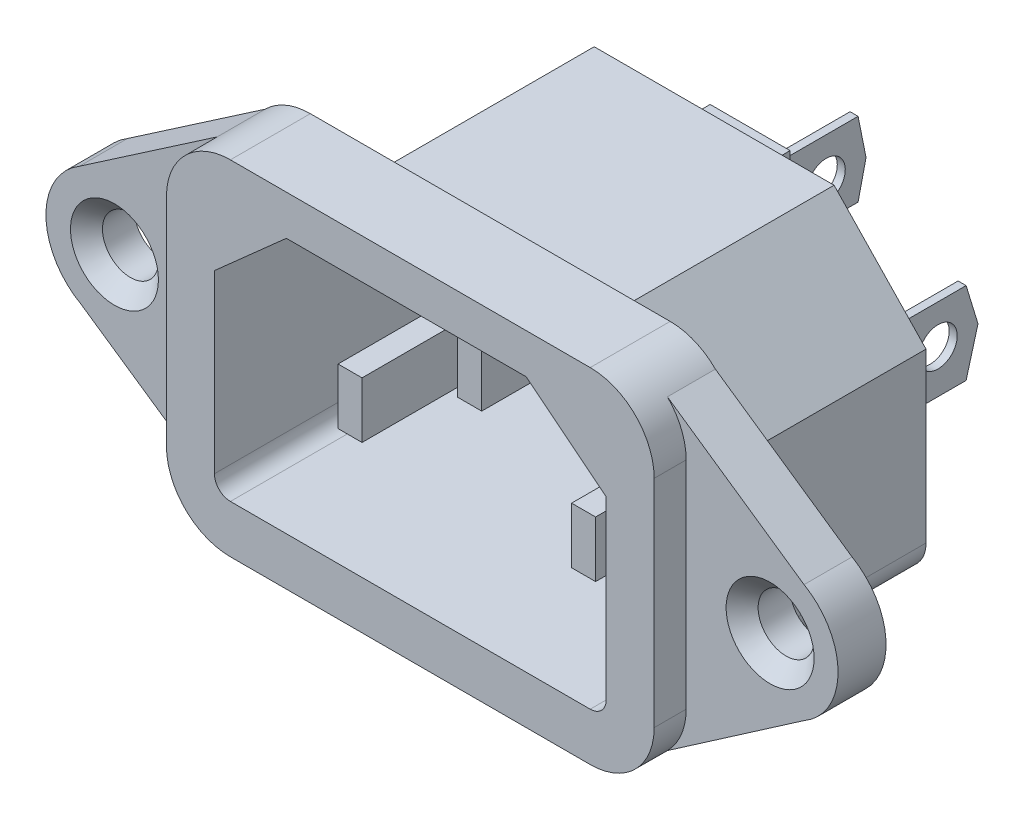
SolidWorks part; units mm, degrees
ref_plane "Спереди" through (0, 0, 0) normal (0, 0, 1) x (1, 0, 0)
ref_plane "Сверху" through (0, 0, 0) normal (0, 1, 0) x (1, 0, 0)
ref_plane "Справа" through (0, 0, 0) normal (1, 0, 0) x (0, 0, -1)
sketch "Эскиз1" plane through (0, 0, 0) normal (0, 0, 1) x (1, 0, 0)
  line L0 (23.0556, -0.5833) -> (-26.4444, -0.5833) construction
  line L1 (-12.9444, 10.1667) -> (9.5556, 10.1667)
  line L2 (-16.9444, 6.1667) -> (-16.9444, -7.3333)
  line L3 (-12.9444, -11.3333) -> (9.5556, -11.3333)
  line L4 (13.5556, 6.1667) -> (13.5556, -7.3333)
  line L5 (-15.7729, 8.9951) -> (-24.3879, 3.0982)
  line L6 (-24.2767, -4.329) -> (-15.7729, -10.1618)
  line L7 (12.384, 8.9951) -> (20.9289, 3.0982)
  line L8 (20.9289, -4.2649) -> (12.384, -10.1618)
  arc A0 (-12.9444, 10.1667) -> (-16.9444, 6.1667) centre (-12.9444, 6.1667) ccw
  arc A1 (-16.9444, -7.3333) -> (-12.9444, -11.3333) centre (-12.9444, -7.3333) ccw
  arc A2 (9.5556, -11.3333) -> (13.5556, -7.3333) centre (9.5556, -7.3333) ccw
  arc A3 (9.5556, 10.1667) -> (13.5556, 6.1667) centre (9.5556, 6.1667) cw
  circle A5 centre (-22.1944, -0.5833) radius 1.75
  circle A6 centre (18.8056, -0.5833) radius 1.75
  arc A7 (20.9289, -4.2649) -> (20.9289, 3.0982) centre (18.8056, -0.5833) ccw
  arc A8 (-24.3879, 3.0982) -> (-24.2767, -4.329) centre (-22.1944, -0.5833) ccw
  point P6 (-16.9444, 10.1667)
  point P11 (13.5556, -11.3333)
  point P14 (13.5556, 10.1667)
  point P21 (-16.9444, -0.5833)
  dimension "D3" = 4
  dimension "D5" = 4.25
  dimension "D6" = 4.25
  dimension "D1" = 30.5
  dimension "D2" = 21.5
  dimension "D4" = 9.5
  dimension "D7" = 5.25
  dimension "D8" = 5.25
extrude "Бобышка-Вытянуть1" add sketch "Эскиз1" against normal blind 3 contours L4 L0 L2 A1 L3 A2 | L0 L4 A3 L1 A0 L2 | A7 L0 A6 L4 A2 L8 | L0 A7 L7 A3 L4 A6 | L5 A8 L6 A1 L2 A5 A0 region at (17.0838, -3.9737, 0) region at (17.0838, 2.8071, 0) region at (-1.6944, -5.8625, 0) region at (-1.6944, 4.6958, 0) region at (-17.1639, -3.9583, 0)
sketch "Эскиз3" plane through (0, 0, 0) normal (0, 0, 1) x (1, 0, 0)
  line L0 (-12.9444, 10.1667) -> (9.5556, 10.1667) construction
  line L1 (-12.9444, 10.1667) -> (9.5556, 10.1667)
  line L2 (-16.9444, 6.1667) -> (-16.9444, -7.3333)
  line L3 (-12.9444, -11.3333) -> (9.5556, -11.3333)
  line L4 (13.5556, 6.1667) -> (13.5556, -7.3333)
  arc A0 (9.5556, 10.1667) -> (13.5556, 6.1667) centre (9.5556, 6.1667) cw
  arc A1 (9.5556, -11.3333) -> (13.5556, -7.3333) centre (9.5556, -7.3333) ccw
  arc A2 (-16.9444, -7.3333) -> (-12.9444, -11.3333) centre (-12.9444, -7.3333) ccw
  arc A3 (-12.9444, 10.1667) -> (-16.9444, 6.1667) centre (-12.9444, 6.1667) ccw
  point P4 (-1.6944, 10.1667)
  point P7 (-1.6944, 10.1667)
  point P10 (13.5556, 10.1667)
  point P15 (-16.9444, -11.3333)
  point P18 (-16.9444, 10.1667)
  dimension "D3" = 4
  dimension "D1" = 30.5
  dimension "D2" = 21.5
extrude "Бобышка-Вытянуть2" add sketch "Эскиз3" along normal blind 2
sketch "Эскиз4" plane through (0, 0, -3) normal (0, 0, -1) x (-1, 0, 0)
  line L0 (1.7119, 8.6668) -> (1.7119, -9.8333) construction
  line L1 (-5.8056, 8.6667) -> (9.1944, 8.6667)
  line L2 (-11.5556, 2.6667) -> (-11.5556, -7.8333)
  line L3 (-9.5556, -9.8333) -> (12.9795, -9.8333)
  line L4 (14.9795, 2.6667) -> (14.9795, -7.8333)
  line L5 (12.9444, 10.1667) -> (-9.5556, 10.1667) construction
  line L6 (12.9444, -11.3333) -> (-9.5556, -11.3333) construction
  line L7 (-11.2855, 2.6667) -> (-11.5556, 2.6667) construction
  line L11 (-11.5556, 2.6667) -> (-5.8056, 8.6667)
  line L12 (9.1944, 8.6667) -> (14.9795, 2.6667)
  arc A0 (-20.9289, 3.0982) -> (-20.9289, -4.2649) centre (-18.8056, -0.5833) ccw construction
  arc A1 (24.2767, -4.329) -> (24.3879, 3.0982) centre (22.1944, -0.5833) ccw construction
  arc A2 (-11.5556, -7.8333) -> (-9.5556, -9.8333) centre (-9.5556, -7.8333) ccw
  arc A3 (12.9795, -9.8333) -> (14.9795, -7.8333) centre (12.9795, -7.8333) ccw
  point P9 (-23.0556, -0.5833)
  point P12 (1.6944, 10.1667)
  point P17 (26.4795, -0.6475)
  point P19 (1.7119, 6.1202)
  dimension "D5" = 2
  dimension "D1" = 11.5
  dimension "D2" = 11.5
  dimension "D3" = 1.5
  dimension "D4" = 1.5
extrude "Бобышка-Вытянуть3" add sketch "Эскиз4" along normal blind 14
sketch "Эскиз5" plane through (0, 0, -3) normal (0, 0, -1) x (-1, 0, 0)
  line L0 (-17.1431, 3.368) -> (-10.047, 8.2024)
  line L1 (-10.047, 8.2024) -> (-8.1409, 8.2024)
  line L2 (-8.1409, 8.2024) -> (-13.1129, 2.8675)
  line L3 (-13.1129, 2.8675) -> (-13.1129, -7.3555)
  line L4 (-13.1129, -7.3555) -> (-17.1431, -4.5346)
  line L5 (20.5354, 3.368) -> (13.5142, 8.2024)
  line L6 (13.5142, 8.2024) -> (11.5035, 8.2024)
  line L7 (11.5035, 8.2024) -> (16.8383, 2.8675)
  line L8 (16.8383, 2.8675) -> (16.8383, -7.0285)
  line L9 (16.8383, -7.0285) -> (20.5354, -4.5346)
  arc A0 (-17.1431, -4.5346) -> (-17.1431, 3.368) centre (-18.8056, -0.5833) ccw
  arc A1 (20.5354, 3.368) -> (20.5354, -4.5346) centre (22.1944, -0.5833) ccw
extrude "Вырез-Вытянуть1" cut sketch "Эскиз5" against normal blind 1
chamfer "Фаска1" distance 1 angle 45 1 edges at (20.5556, -0.5833, 0)
chamfer "Фаска2" distance 1 angle 45 1 edges at (-20.4444, -0.5833, 0)
sketch "Эскиз6" plane through (0, 0, -17) normal (0, 0, -1) x (-1, 0, 0)
  line L0 (9.1944, 8.6667) -> (-5.8056, 8.6667) construction
  line L1 (-8.0556, 1.6667) -> (-3.0556, 1.6667)
  line L2 (-8.0556, 1.6667) -> (-8.0556, -8.3333)
  line L3 (-8.0556, -8.3333) -> (-3.0556, -8.3333)
  line L4 (-3.0556, 1.6667) -> (-3.0556, -8.3333)
  line L5 (-8.0556, 1.6667) -> (-3.0556, -8.3333) construction
  line L6 (-8.0556, -8.3333) -> (-3.0556, 1.6667) construction
  line L7 (-1.0556, 7.1667) -> (3.9444, 7.1667)
  line L8 (-1.0556, 7.1667) -> (-1.0556, -2.8333)
  line L9 (-1.0556, -2.8333) -> (3.9444, -2.8333)
  line L10 (3.9444, 7.1667) -> (3.9444, -2.8333)
  line L11 (-1.0556, 7.1667) -> (3.9444, -2.8333) construction
  line L12 (-1.0556, -2.8333) -> (3.9444, 7.1667) construction
  line L13 (6.4795, 1.6667) -> (11.4795, 1.6667)
  line L14 (6.4795, 1.6667) -> (6.4795, -8.3333)
  line L15 (6.4795, -8.3333) -> (11.4795, -8.3333)
  line L16 (11.4795, 1.6667) -> (11.4795, -8.3333)
  line L17 (6.4795, 1.6667) -> (11.4795, -8.3333) construction
  line L18 (6.4795, -8.3333) -> (11.4795, 1.6667) construction
  line L19 (9.1944, 8.6667) -> (-5.8056, 8.6667) construction
  line L20 (-11.5556, 2.6667) -> (-11.5556, -7.8333) construction
  line L21 (14.9795, -7.8333) -> (14.9795, 2.6667) construction
  line L22 (-9.5556, -9.8333) -> (12.9795, -9.8333) construction
  line L23 (-11.5556, 2.6667) -> (-11.5556, -7.8333) construction
  point P0 (-5.5556, -3.3333)
  point P5 (1.4444, 2.1667)
  point P10 (8.9795, -3.3333)
  dimension "D1" = 5
  dimension "D2" = 10
  dimension "D3" = 5
  dimension "D4" = 10
  dimension "D5" = 5
  dimension "D6" = 10
  dimension "D7" = 7
  dimension "D8" = 7
  dimension "D9" = 3.5
  dimension "D10" = 3.5
  dimension "D11" = 7
  dimension "D12" = 10.5
extrude "Бобышка-Вытянуть4" add sketch "Эскиз6" along normal blind 2
sketch "Эскиз7" plane through (0, 0, -19) normal (0, 0, -1) x (-1, 0, 0)
  line L0 (-8.0556, -8.3333) -> (-3.0556, -8.3333) construction
  line L1 (-5.8056, 0.6667) -> (-5.3056, 0.6667)
  line L2 (-5.8056, 0.6667) -> (-5.8056, -7.3333)
  line L3 (-5.8056, -7.3333) -> (-5.3056, -7.3333)
  line L4 (-5.3056, 0.6667) -> (-5.3056, -7.3333)
  line L5 (-8.0556, 1.6667) -> (-8.0556, -8.3333) construction
  line L7 (11.4795, -8.3333) -> (11.4795, 1.6667) construction
  line L8 (1.1944, 6.1667) -> (1.6944, 6.1667)
  line L9 (1.1944, 6.1667) -> (1.1944, -1.8333)
  line L10 (1.1944, -1.8333) -> (1.6944, -1.8333)
  line L11 (1.6944, 6.1667) -> (1.6944, -1.8333)
  line L12 (8.7295, 0.6667) -> (9.2295, 0.6667)
  line L13 (8.7295, 0.6667) -> (8.7295, -7.3333)
  line L14 (8.7295, -7.3333) -> (9.2295, -7.3333)
  line L15 (9.2295, 0.6667) -> (9.2295, -7.3333)
  line L16 (3.9444, -2.8333) -> (3.9444, 7.1667) construction
  line L17 (-1.0556, -2.8333) -> (3.9444, -2.8333) construction
  line L18 (6.4795, -8.3333) -> (11.4795, -8.3333) construction
  dimension "D1" = 0.5
  dimension "D2" = 8
  dimension "D3" = 1
  dimension "D4" = 2.25
  dimension "D5" = 0.5
  dimension "D6" = 8
  dimension "D7" = 0.5
  dimension "D8" = 8
  dimension "D9" = 2.25
  dimension "D10" = 2.25
  dimension "D11" = 1
  dimension "D12" = 1
extrude "Бобышка-Вытянуть5" add sketch "Эскиз7" along normal mid plane 14
sketch "Эскиз8" plane through (-9.2295, 0, 0) normal (-1, 0, 0) x (0, 0, 1)
  line L0 (-26, -3.3333) -> (-19, -3.3333) construction
  line L1 (-26, -3.3333) -> (-25.8529, -5.083)
  line L2 (-25.8529, -5.083) -> (-20.6676, -5.083)
  line L3 (-20.6676, -5.083) -> (-20.2818, -5.4689)
  line L4 (-19, -7.048) -> (-19, -7.3333)
  line L5 (-19, -7.3333) -> (-19, 0.6667) construction
  line L6 (-26, -7.3333) -> (-19, -7.3333) construction
  line L7 (-19, -7.3333) -> (-26, -7.3333)
  line L12 (-20.2818, -5.4689) -> (-19.1592, -5.4689)
  line L13 (-19.1592, -5.4689) -> (-20.0283, -7.1824)
  line L14 (-20.0283, -7.1824) -> (-19, -7.048)
  line L15 (-26, -7.3333) -> (-26, 0.6667)
  line L16 (-19, 0.6667) -> (-26, 0.6667)
  line L17 (-19, 0.3813) -> (-19, 0.6667)
  line L18 (-20.0283, 0.5157) -> (-19, 0.3813)
  line L19 (-19.1592, -1.1978) -> (-20.0283, 0.5157)
  line L20 (-20.2818, -1.1978) -> (-19.1592, -1.1978)
  line L21 (-20.6676, -1.5836) -> (-20.2818, -1.1978)
  line L22 (-25.8529, -1.5836) -> (-20.6676, -1.5836)
  line L23 (-26, -3.3333) -> (-25.8529, -1.5836)
  circle A0 centre (-23.4767, -3.3333) radius 1.2
  line M15 (-19, -7.3333) -> (-19, 0.6667)
  line M16 (-19, 0.6667) -> (-26, 0.6667)
  line M17 (-26, 0.6667) -> (-26, -7.3333)
  line M18 (-26, -7.3333) -> (-19, -7.3333)
extrude "Вырез-Вытянуть2" cut sketch "Эскиз8" against normal blind 3 contours L23 L22 L21 L20 L19 L18 M17 M15 M16 | L14 L13 L12 L3 L2 L1 M17 M18 M15 | A0 region at (-9.2295, -6.2115, -22.8481) region at (-9.2295, -0.4552, -22.8481)
sketch "Эскиз11" plane through (-1.6944, 0, 0) normal (-1, 0, 0) x (0, 0, 1)
  line L0 (-26, 2.1667) -> (-19, 2.1667) construction
  line L1 (-26, -1.8333) -> (-26, 6.1667) construction
  line L2 (-19, -1.8333) -> (-19, 6.1667) construction
  line L3 (-25.5002, 0) -> (-26, 2.1667)
  line L4 (-26, 6.1667) -> (-19, 6.1667)
  line L5 (-26, 6.1667) -> (-26, 4.6488)
  line L6 (-25.5002, 4.6488) -> (-19, 4.6488)
  line L7 (-19, 6.1667) -> (-19, 4.6488)
  line L8 (-26, -1.8333) -> (-19, -1.8333)
  line L9 (-26, -1.8333) -> (-26, 0)
  line L10 (-25.5002, 0) -> (-19, 0)
  line L11 (-19, -1.8333) -> (-19, 0)
  line L12 (-26, 2.1667) -> (-26, 0)
  line L13 (-26, 2.1667) -> (-25.5002, 4.6488)
  line L14 (-26, 2.1667) -> (-26, 4.6488)
  circle A0 centre (-23.5, 2.1667) radius 1.2
  line M14 (-19, -1.8333) -> (-19, 6.1667)
  line M15 (-19, 6.1667) -> (-26, 6.1667)
  line M16 (-26, 6.1667) -> (-26, -1.8333)
  line M17 (-26, -1.8333) -> (-19, -1.8333)
  dimension "D1" = 2.5
extrude "Вырез-Вытянуть3" cut sketch "Эскиз11" against normal blind 3 contours L0 A0 | A0 L0 | L13 L6 M16 M14 M15 | L10 L3 M16 M17 M14 region at (-1.6944, 1.6574, -23.5) region at (-1.6944, 2.676, -23.5) region at (-1.6944, -0.8503, -22.6349) region at (-1.6944, 5.3202, -22.6839)
sketch "Эскиз12" plane through (5.3056, 0, 0) normal (-1, 0, 0) x (0, 0, 1)
  line L0 (-26, -3.3333) -> (-19, -3.3333) construction
  line L1 (-26, -7.3333) -> (-26, 0.6667) construction
  line L2 (-19, -7.3333) -> (-19, 0.6667) construction
  line L3 (-25.2563, -6.0356) -> (-26, -3.3333)
  line L4 (-26, -7.3333) -> (-19, -7.3333)
  line L5 (-26, -7.3333) -> (-26, -6.0356)
  line L6 (-25.2563, -6.0356) -> (-19, -6.0356)
  line L7 (-19, -7.3333) -> (-19, -6.0356)
  line L8 (-26, 0.6667) -> (-19, 0.6667)
  line L9 (-26, 0.6667) -> (-26, -0.8964)
  line L10 (-25.2563, -0.8964) -> (-19, -0.8964)
  line L11 (-19, 0.6667) -> (-19, -0.8964)
  line L12 (-26, -3.3333) -> (-26, -6.0356)
  line L13 (-26, -3.3333) -> (-25.2563, -0.8964)
  line L14 (-26, -3.3333) -> (-26, -0.8964)
  circle A0 centre (-23.5, -3.3333) radius 1.2
  line M13 (-19, -7.3333) -> (-19, 0.6667)
  line M14 (-19, 0.6667) -> (-26, 0.6667)
  line M15 (-26, 0.6667) -> (-26, -7.3333)
  line M16 (-26, -7.3333) -> (-19, -7.3333)
  dimension "D1" = 2.5
extrude "Вырез-Вытянуть4" cut sketch "Эскиз12" against normal blind 3 contours L13 L10 M15 M13 M14 | L6 L3 M15 M16 M13 | L0 A0 | A0 L0 region at (5.3056, -3.8426, -23.5) region at (5.3056, -2.824, -23.5) region at (5.3056, -6.5301, -22.8239) region at (5.3056, -0.2368, -22.7487)
sketch "Эскиз15" plane through (0, 0, 2) normal (0, 0, 1) x (1, 0, 0)
  line L0 (9.5556, 10.1667) -> (-12.9444, 10.1667) construction
  line L1 (-9.4444, 7.6667) -> (5.5556, 7.6667)
  line L2 (-13.9444, 3.6667) -> (-13.9444, -7.3333)
  line L3 (-12.9444, -8.3333) -> (9.5556, -8.3333)
  line L4 (10.5556, 3.6667) -> (10.5556, -7.3333)
  line L5 (-16.9444, 6.1667) -> (-16.9444, -7.3333) construction
  line L10 (-1.6944, -8.3333) -> (-1.6944, 7.6667) construction
  line L14 (-9.4444, 7.6667) -> (-13.9444, 3.6667)
  line L15 (5.5556, 7.6667) -> (10.5556, 3.6667)
  arc A0 (9.5556, -8.3333) -> (10.5556, -7.3333) centre (9.5556, -7.3333) ccw
  arc A1 (-13.9444, -7.3333) -> (-12.9444, -8.3333) centre (-12.9444, -7.3333) ccw
  point P19 (-1.9444, 7.6667)
  point P20 (-1.6944, 6.231)
  point P21 (-1.6944, 6.231)
  dimension "D1" = 1
  dimension "D3" = 2.5
  dimension "D4" = 3
extrude "Вырез-Вытянуть6" cut sketch "Эскиз15" against normal blind 17
sketch "Эскиз16" plane through (0, 0, -19) normal (0, 0, -1) x (-1, 0, 0)
  line L0 (6.4795, 1.6667) -> (6.4795, -8.3333) construction
  line L1 (6.4795, -8.3333) -> (11.4795, -8.3333) construction
  line L2 (11.4795, -8.3333) -> (11.4795, 1.6667) construction
  line L3 (11.4795, 1.6667) -> (6.4795, 1.6667) construction
  line L4 (-1.0556, 7.1667) -> (-1.0556, -2.8333) construction
  line L5 (-1.0556, -2.8333) -> (3.9444, -2.8333) construction
  line L6 (3.9444, -2.8333) -> (3.9444, 7.1667) construction
  line L7 (3.9444, 7.1667) -> (-1.0556, 7.1667) construction
  line L8 (-8.0556, 1.6667) -> (-8.0556, -8.3333) construction
  line L9 (-8.0556, -8.3333) -> (-3.0556, -8.3333) construction
  line L10 (-3.0556, -8.3333) -> (-3.0556, 1.6667) construction
  line L11 (-3.0556, 1.6667) -> (-8.0556, 1.6667) construction
  line L12 (6.4795, 1.6667) -> (6.4795, -8.3333)
  line L13 (6.4795, -8.3333) -> (11.4795, -8.3333)
  line L14 (11.4795, -8.3333) -> (11.4795, 1.6667)
  line L15 (11.4795, 1.6667) -> (6.4795, 1.6667)
  line L16 (-1.0556, 7.1667) -> (-1.0556, -2.8333)
  line L17 (-1.0556, -2.8333) -> (3.9444, -2.8333)
  line L18 (3.9444, -2.8333) -> (3.9444, 7.1667)
  line L19 (3.9444, 7.1667) -> (-1.0556, 7.1667)
  line L20 (-8.0556, 1.6667) -> (-8.0556, -8.3333)
  line L21 (-8.0556, -8.3333) -> (-3.0556, -8.3333)
  line L22 (-3.0556, -8.3333) -> (-3.0556, 1.6667)
  line L23 (-3.0556, 1.6667) -> (-8.0556, 1.6667)
extrude "Бобышка-Вытянуть7" add sketch "Эскиз16" against normal blind 5
sketch "Эскиз17" plane through (0, 0, -14) normal (0, 0, 1) x (1, 0, 0)
  line L1 (-9.7114, -1.0234) -> (-8.2114, -1.0234)
  line L2 (-9.7114, -1.0234) -> (-9.7114, -4.5234)
  line L3 (-9.7114, -4.5234) -> (-8.2114, -4.5234)
  line L4 (-8.2114, -1.0234) -> (-8.2114, -4.5234)
  line L5 (-2.2287, 4.415) -> (-0.7287, 4.415)
  line L6 (-2.2287, 4.415) -> (-2.2287, 0.915)
  line L7 (-2.2287, 0.915) -> (-0.7287, 0.915)
  line L8 (-0.7287, 4.415) -> (-0.7287, 0.915)
  line L9 (4.892, -1.2569) -> (6.392, -1.2569)
  line L10 (4.892, -1.2569) -> (4.892, -4.7569)
  line L11 (4.892, -4.7569) -> (6.392, -4.7569)
  line L12 (6.392, -1.2569) -> (6.392, -4.7569)
  dimension "D1" = 1.5
  dimension "D2" = 3.5
  dimension "D3" = 1.5
  dimension "D4" = 3.5
  dimension "D5" = 1.5
  dimension "D6" = 3.5
extrude "Бобышка-Вытянуть8" add sketch "Эскиз17" along normal blind 12.5
